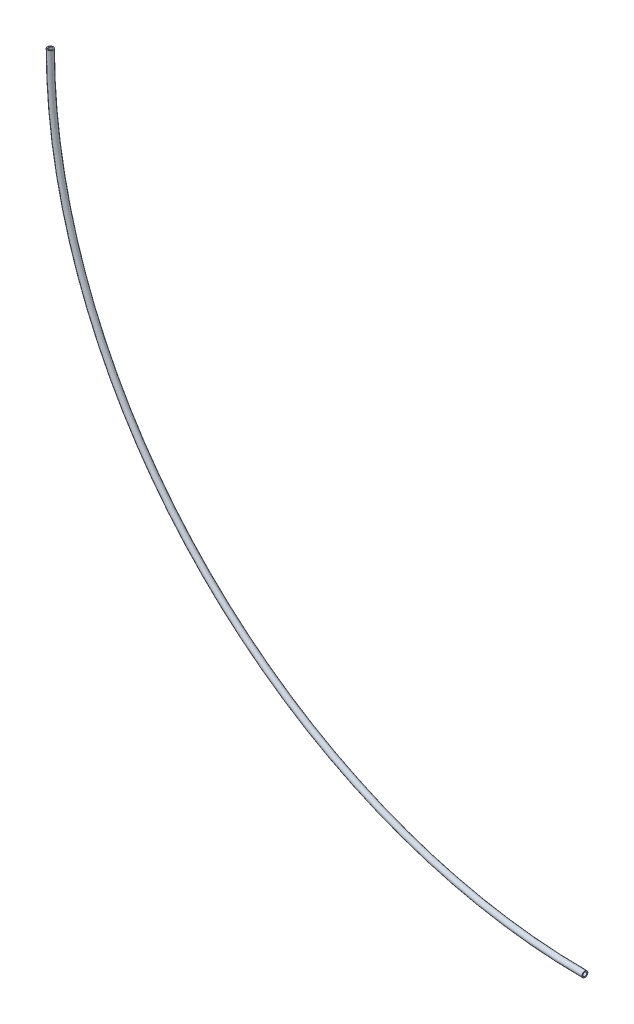
SolidWorks part; units mm, degrees
ref_plane "前视基准面" through (0, 0, 0) normal (0, 0, 1) x (1, 0, 0)
ref_plane "上视基准面" through (0, 0, 0) normal (0, 1, 0) x (1, 0, 0)
ref_plane "右视基准面" through (0, 0, 0) normal (1, 0, 0) x (0, 0, -1)
sketch "草图1" plane through (0, 0, 0) normal (0, 0, 1) x (1, 0, 0)
  circle A0 centre (0, 0) radius 1100 construction
  arc A1 (-1100, 0) -> (0, -1100) centre (0, 0) ccw
  dimension "D1" = 2200
sweep "扫描-薄件1" add path "草图1" circular profile diameter 12 parameters "D1"=2, "D3"=12
